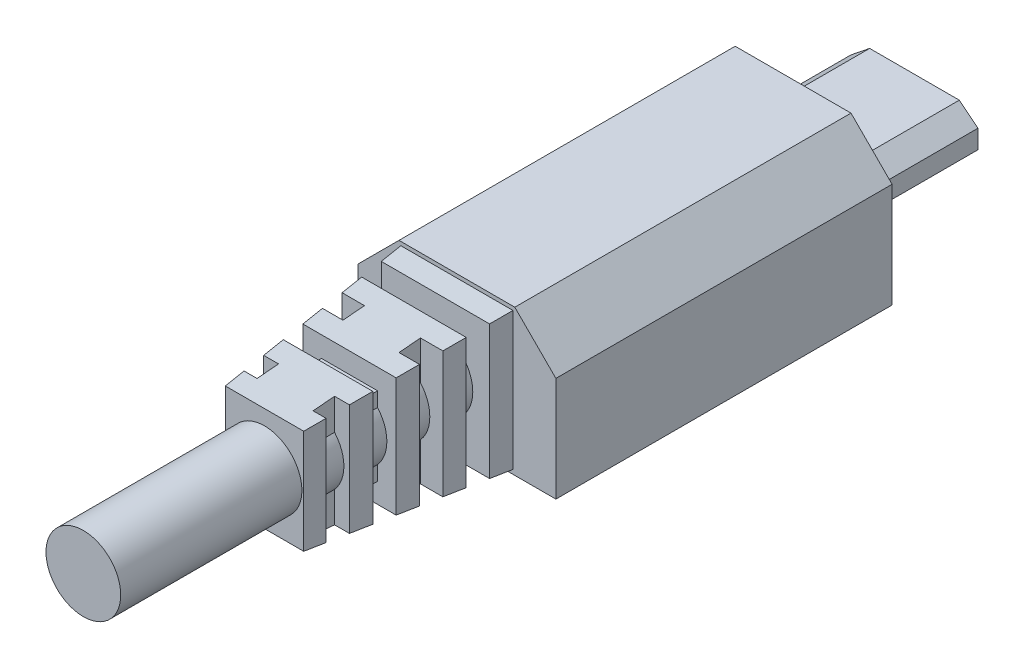
SolidWorks part; units mm, degrees
ref_plane "Front Plane" through (0, 0, 0) normal (0, 0, 1) x (1, 0, 0)
ref_plane "Top Plane" through (0, 0, 0) normal (0, 1, 0) x (1, 0, 0)
ref_plane "Right Plane" through (0, 0, 0) normal (1, 0, 0) x (0, 0, -1)
sketch "Sketch1" plane through (0, 0, 0) normal (0, 0, 1) x (1, 0, 0)
  line L0 (0, 1) -> (1, 1.8)
  line L1 (0, 0) -> (6.8, 0)
  line L2 (0, 0) -> (0, 1.8)
  line L3 (0, 1.8) -> (6.8, 1.8)
  line L4 (6.8, 0) -> (6.8, 1.8)
  line L5 (3.4, 1.8) -> (3.4, 0) construction
  line L6 (6.8, 1) -> (5.8, 1.8)
  line L8 (1.55, 0.2) -> (5.25, 0.2)
  line L9 (1.55, 0.2) -> (1.55, 0.85)
  line L10 (1.55, 0.85) -> (5.25, 0.85)
  line L11 (5.25, 0.2) -> (5.25, 0.85)
  point P15 (3.4, 0.85)
  dimension "D1" = 1.8
  dimension "D2" = 6.8
  dimension "D3" = 1
  dimension "D4" = 1
  dimension "D5" = 0.2
  dimension "D6" = 3.7
  dimension "D7" = 0.65
extrude "Boss-Extrude1" add sketch "Sketch1" along normal blind 6.5 contours L5 L3 L0 L2 L1 L8 L9 L10 | L3 L5 L10 L11 L8 L1 L4 L6 region at (1.6147, 0.9437, 0) region at (5.1853, 0.9437, 0)
sketch "Sketch2" plane through (0, 0, 6.5) normal (0, 0, 1) x (1, 0, 0)
  line L0 (0, 0.7631) -> (-1.9, 0.7631) construction
  line L1 (-1.9, 4.8) -> (8.7, 4.8)
  line L2 (-1.9, 4.8) -> (-1.9, -3)
  line L3 (-1.9, -3) -> (8.7, -3)
  line L4 (8.7, 4.8) -> (8.7, -3)
  line L5 (-1.9, 2.6) -> (0.3, 4.8)
  line L6 (8.7, 2.6) -> (6.5, 4.8)
  line L7 (3.4, 4.8) -> (3.4, 1.8) construction
  line L8 (1, 1.8) -> (5.8, 1.8) construction
  line L9 (3.4, 0) -> (3.4, -3) construction
  line L10 (0, 0) -> (6.8, 0) construction
  line L13 (0, 0) -> (0, 1) construction
  line L14 (6.8, 0.7631) -> (8.7, 0.7631) construction
  line L15 (6.8, 0) -> (6.8, 1) construction
  line M1 (1.55, 0.85) -> (5.25, 0.85)
  line M2 (5.25, 0.85) -> (5.25, 0.2)
  line M3 (5.25, 0.2) -> (1.55, 0.2)
  line M4 (1.55, 0.2) -> (1.55, 0.85)
  line M5 (6.8, 1) -> (5.8, 1.8)
  line M6 (5.8, 1.8) -> (1, 1.8)
  line M7 (1, 1.8) -> (0, 1)
  line M8 (0, 1) -> (0, 0)
  line M9 (0, 0) -> (6.8, 0)
  line M10 (6.8, 0) -> (6.8, 1)
  dimension "D1" = 10.6
  dimension "D2" = 7.8
  dimension "D3" = 2.2
  dimension "D4" = 2.2
extrude "Boss-Extrude2" add sketch "Sketch2" along normal blind 18 contours L4 L6 L1 L5 L2 L3 M5 M10 M9 M8 M7 M6 | M10 M5 M6 M7 M8 M9 M4 M1 M2 M3 | M1 M4 M3 M2 region at (3.4, 4.6684, 6.5) region at (3.4, 0.525, 6.5) region at (3.4, 0.9437, 6.5)
sketch "Sketch5" plane through (0, 0, 24.5) normal (0, 0, 1) x (1, 0, 0)
  line L0 (0.3, 4.8) -> (6.5, 4.8) construction
  line L1 (6.4, 4.6) -> (0.4, 4.6)
  line L2 (6.4, 4.6) -> (6.4, -2.772)
  line L3 (6.4, -2.772) -> (0.4, -2.772)
  line L4 (0.4, 4.6) -> (0.4, -2.772)
  line L6 (3.4, 4.8) -> (3.4, 4.6) construction
  dimension "D1" = 0.2
  dimension "D2" = 6
extrude "Boss-Extrude4" add sketch "Sketch5" along normal blind 10.3 draft 5
sketch "Sketch7" plane through (0, 4.8, 0) normal (0, 1, 0) x (1, 0, 0)
  line L0 (3.4, -24.5) -> (3.4, -36.1996) construction
  line L1 (0.3, -24.5) -> (1.9, -24.5)
  line L2 (0.3, -24.5) -> (0.3, -25.65)
  line L3 (0.3, -25.65) -> (1.9, -25.65)
  line L4 (1.9, -24.5) -> (1.9, -25.65)
  line L5 (1.9, -25.65) -> (-0.2696, -25.65)
  line L6 (1.9, -25.65) -> (1.9, -26.8)
  line L7 (1.9, -26.8) -> (-0.2696, -26.8)
  line L8 (-0.2696, -25.65) -> (-0.2696, -26.8)
  line L9 (1.9, -26.8) -> (-0.2696, -26.8)
  line L10 (1.9, -26.8) -> (1.9, -27.95)
  line L11 (1.9, -27.95) -> (-0.2696, -27.95)
  line L12 (-0.2696, -26.8) -> (-0.2696, -27.95)
  line L13 (1.9, -27.95) -> (-0.2696, -27.95)
  line L14 (1.9, -27.95) -> (1.9, -29.1)
  line L15 (1.9, -29.1) -> (-0.2696, -29.1)
  line L16 (-0.2696, -27.95) -> (-0.2696, -29.1)
  line L17 (1.9, -29.1) -> (-0.2696, -29.1)
  line L18 (1.9, -29.1) -> (1.9, -30.25)
  line L19 (1.9, -30.25) -> (-0.2696, -30.25)
  line L20 (-0.2696, -29.1) -> (-0.2696, -30.25)
  line L21 (1.9, -30.25) -> (-0.2696, -30.25)
  line L22 (1.9, -30.25) -> (1.9, -31.4)
  line L23 (1.9, -31.4) -> (-0.2696, -31.4)
  line L24 (-0.2696, -30.25) -> (-0.2696, -31.4)
  line L25 (1.9, -31.4) -> (-0.2696, -31.4)
  line L26 (1.9, -31.4) -> (1.9, -32.55)
  line L27 (1.9, -32.55) -> (-0.2696, -32.55)
  line L28 (-0.2696, -31.4) -> (-0.2696, -32.55)
  line L29 (1.9, -32.55) -> (-0.2696, -32.55)
  line L30 (1.9, -32.55) -> (1.9, -33.7)
  line L31 (1.9, -33.7) -> (-0.2696, -33.7)
  line L32 (-0.2696, -32.55) -> (-0.2696, -33.7)
  line L33 (1.9, -33.7) -> (-0.2696, -33.7)
  line L34 (1.9, -33.7) -> (1.9, -34.85)
  line L35 (1.9, -34.85) -> (-0.2696, -34.85)
  line L36 (-0.2696, -33.7) -> (-0.2696, -34.85)
  line L37 (6.4, -24.5) -> (0.4, -24.5) construction
  line L38 (7.0696, -33.7) -> (7.0696, -34.85)
  line L39 (4.9, -34.85) -> (7.0696, -34.85)
  line L40 (4.9, -33.7) -> (4.9, -34.85)
  line L41 (4.9, -33.7) -> (7.0696, -33.7)
  line L42 (7.0696, -32.55) -> (7.0696, -33.7)
  line L43 (4.9, -33.7) -> (7.0696, -33.7)
  line L44 (4.9, -32.55) -> (4.9, -33.7)
  line L45 (4.9, -32.55) -> (7.0696, -32.55)
  line L46 (7.0696, -31.4) -> (7.0696, -32.55)
  line L47 (4.9, -32.55) -> (7.0696, -32.55)
  line L48 (4.9, -31.4) -> (4.9, -32.55)
  line L49 (4.9, -31.4) -> (7.0696, -31.4)
  line L50 (7.0696, -30.25) -> (7.0696, -31.4)
  line L51 (4.9, -31.4) -> (7.0696, -31.4)
  line L52 (4.9, -30.25) -> (4.9, -31.4)
  line L53 (4.9, -30.25) -> (7.0696, -30.25)
  line L54 (7.0696, -29.1) -> (7.0696, -30.25)
  line L55 (4.9, -30.25) -> (7.0696, -30.25)
  line L56 (4.9, -29.1) -> (4.9, -30.25)
  line L57 (4.9, -29.1) -> (7.0696, -29.1)
  line L58 (7.0696, -27.95) -> (7.0696, -29.1)
  line L59 (4.9, -29.1) -> (7.0696, -29.1)
  line L60 (4.9, -27.95) -> (4.9, -29.1)
  line L61 (4.9, -27.95) -> (7.0696, -27.95)
  line L62 (7.0696, -26.8) -> (7.0696, -27.95)
  line L63 (4.9, -27.95) -> (7.0696, -27.95)
  line L64 (4.9, -26.8) -> (4.9, -27.95)
  line L65 (4.9, -26.8) -> (7.0696, -26.8)
  line L66 (7.0696, -25.65) -> (7.0696, -26.8)
  line L67 (4.9, -26.8) -> (7.0696, -26.8)
  line L68 (4.9, -25.65) -> (4.9, -26.8)
  line L69 (4.9, -25.65) -> (7.0696, -25.65)
  line L70 (4.9, -24.5) -> (4.9, -25.65)
  line L71 (6.5, -25.65) -> (4.9, -25.65)
  line L72 (6.5, -24.5) -> (6.5, -25.65)
  line L73 (6.5, -24.5) -> (4.9, -24.5)
  dimension "D1" = 1.15
  dimension "D2" = 1.6
extrude "Cut-Extrude1" cut sketch "Sketch7" against normal blind 10.3 contours L5 L8 L7 L6 L3 | L11 L16 L15 L14 | L19 L24 L23 L22 | L27 L32 L31 L30 | L69 L68 L65 L66 | L61 L60 L57 L58 | L53 L52 L49 L50 | L45 L44 L41 L42 region at (0.8152, 4.8, 26.225) region at (0.8152, 4.8, 28.525) region at (0.8152, 4.8, 30.825) region at (0.8152, 4.8, 33.125) region at (5.9848, 4.8, 33.125) region at (5.9848, 4.8, 30.825) region at (5.9848, 4.8, 28.525) region at (5.9848, 4.8, 26.225)
ref_plane "Plane1" through (6.4, -2.772, 24.5) normal (0, 1, 0) x (1, 0, 0)
sketch "Sketch9" plane through (8.7, 0, 0) normal (1, 0, 0) x (0, 0, -1)
  line L0 (-36.8785, 0.9) -> (-25.1788, 0.9) construction
  line L1 (-34.85, -2.8) -> (-34.85, -1.2)
  line L2 (-34.85, -2.8) -> (-33.7, -2.8)
  line L3 (-33.7, -2.8) -> (-33.7, -1.2)
  line L4 (-34.85, -1.2) -> (-33.7, -1.2)
  line L5 (-33.7, -1.2) -> (-33.7, -2.8)
  line L6 (-33.7, -1.2) -> (-32.55, -1.2)
  line L7 (-32.55, -1.2) -> (-32.55, -2.8)
  line L8 (-33.7, -2.8) -> (-32.55, -2.8)
  line L9 (-32.55, -1.2) -> (-32.55, -2.8)
  line L10 (-32.55, -1.2) -> (-31.4, -1.2)
  line L11 (-31.4, -1.2) -> (-31.4, -2.8)
  line L12 (-32.55, -2.8) -> (-31.4, -2.8)
  line L13 (-31.4, -1.2) -> (-31.4, -2.8)
  line L14 (-31.4, -1.2) -> (-30.25, -1.2)
  line L15 (-30.25, -1.2) -> (-30.25, -2.8)
  line L16 (-31.4, -2.8) -> (-30.25, -2.8)
  line L17 (-30.25, -1.2) -> (-30.25, -2.8)
  line L18 (-30.25, -1.2) -> (-29.1, -1.2)
  line L19 (-29.1, -1.2) -> (-29.1, -2.8)
  line L20 (-30.25, -2.8) -> (-29.1, -2.8)
  line L21 (-29.1, -1.2) -> (-29.1, -2.8)
  line L22 (-29.1, -1.2) -> (-27.95, -1.2)
  line L23 (-27.95, -1.2) -> (-27.95, -2.8)
  line L24 (-29.1, -2.8) -> (-27.95, -2.8)
  line L25 (-27.95, -1.2) -> (-27.95, -2.8)
  line L26 (-27.95, -1.2) -> (-26.8, -1.2)
  line L27 (-26.8, -1.2) -> (-26.8, -2.8)
  line L28 (-27.95, -2.8) -> (-26.8, -2.8)
  line L29 (-26.8, -1.2) -> (-26.8, -2.8)
  line L30 (-26.8, -1.2) -> (-25.65, -1.2)
  line L31 (-25.65, -1.2) -> (-25.65, -2.8)
  line L32 (-26.8, -2.8) -> (-25.65, -2.8)
  line L33 (-25.65, -1.2) -> (-25.65, -2.8)
  line L34 (-25.65, -1.2) -> (-24.5, -1.2)
  line L35 (-24.5, -1.2) -> (-24.5, -2.8)
  line L36 (-25.65, -2.8) -> (-24.5, -2.8)
  line L37 (-25.65, 4.6) -> (-24.5, 4.6)
  line L38 (-24.5, 3) -> (-24.5, 4.6)
  line L39 (-25.65, 3) -> (-24.5, 3)
  line L40 (-25.65, 3) -> (-25.65, 4.6)
  line L41 (-26.8, 4.6) -> (-25.65, 4.6)
  line L42 (-25.65, 3) -> (-25.65, 4.6)
  line L43 (-26.8, 3) -> (-25.65, 3)
  line L44 (-26.8, 3) -> (-26.8, 4.6)
  line L45 (-27.95, 4.6) -> (-26.8, 4.6)
  line L46 (-26.8, 3) -> (-26.8, 4.6)
  line L47 (-27.95, 3) -> (-26.8, 3)
  line L48 (-27.95, 3) -> (-27.95, 4.6)
  line L49 (-29.1, 4.6) -> (-27.95, 4.6)
  line L50 (-27.95, 3) -> (-27.95, 4.6)
  line L51 (-29.1, 3) -> (-27.95, 3)
  line L52 (-29.1, 3) -> (-29.1, 4.6)
  line L53 (-30.25, 4.6) -> (-29.1, 4.6)
  line L54 (-29.1, 3) -> (-29.1, 4.6)
  line L55 (-30.25, 3) -> (-29.1, 3)
  line L56 (-30.25, 3) -> (-30.25, 4.6)
  line L57 (-31.4, 4.6) -> (-30.25, 4.6)
  line L58 (-30.25, 3) -> (-30.25, 4.6)
  line L59 (-31.4, 3) -> (-30.25, 3)
  line L60 (-31.4, 3) -> (-31.4, 4.6)
  line L61 (-32.55, 4.6) -> (-31.4, 4.6)
  line L62 (-31.4, 3) -> (-31.4, 4.6)
  line L63 (-32.55, 3) -> (-31.4, 3)
  line L64 (-32.55, 3) -> (-32.55, 4.6)
  line L65 (-33.7, 4.6) -> (-32.55, 4.6)
  line L66 (-32.55, 3) -> (-32.55, 4.6)
  line L67 (-33.7, 3) -> (-32.55, 3)
  line L68 (-33.7, 3) -> (-33.7, 4.6)
  line L69 (-34.85, 3) -> (-33.7, 3)
  line L70 (-33.7, 4.6) -> (-33.7, 3)
  line L71 (-34.85, 4.6) -> (-33.7, 4.6)
  line L72 (-34.85, 4.6) -> (-34.85, 3)
  dimension "D1" = 1.15
  dimension "D2" = 1.6
  dimension "D3" = 2.1
extrude "Cut-Extrude2" cut sketch "Sketch9" against normal blind 10.3 contours L44 L43 L40 L41 | L60 L59 L56 L57 | L27 L32 L31 L30 | L11 L16 L15 L14 region at (8.7, -2, 30.825) region at (8.7, -2, 26.225) region at (8.7, 3.8, 26.225) region at (8.7, 3.8, 30.825)
sketch "Sketch3" plane through (0, 0, 24.5) normal (0, 0, 1) x (1, 0, 0)
  line L0 (3.4, 4.8) -> (3.4, 0.9) construction
  line L1 (0.3, 4.8) -> (6.5, 4.8) construction
  line L2 (3.4, 0.9) -> (-1.9, 0.9) construction
  line L3 (-1.9, 2.6) -> (-1.9, -3) construction
  line L4 (3.4, 0.9) -> (3.4, -3) construction
  line L5 (-1.9, -3) -> (8.7, -3) construction
  line L6 (3.4, 0.9) -> (8.7, 0.9) construction
  line L7 (8.7, 2.6) -> (8.7, -3) construction
  line L8 (8.7, 4.8) -> (8.7, -3) construction
  circle A0 centre (3.4, 0.9) radius 2
extrude "Boss-Extrude3" add sketch "Sketch3" along normal blind 20
